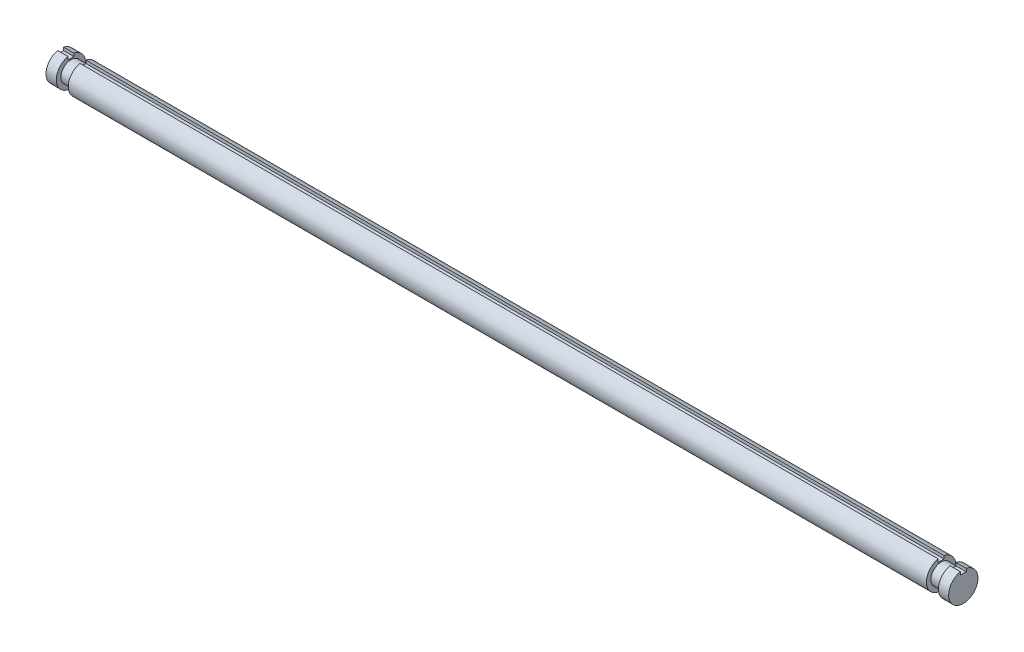
SolidWorks part; units mm, degrees
ref_plane "Front Plane" through (0, 0, 0) normal (1, 0, 0) x (0, 1, 0)
ref_plane "Top Plane" through (0, 0, 0) normal (0, 0, 1) x (0, 1, 0)
ref_plane "Right Plane" through (0, 0, 0) normal (0, 1, 0) x (-1, 0, 0)
sketch "Sketch1" plane through (0, 0, 0) normal (0, 0, 1) x (0, 1, 0)
  line L0 (0, 0) -> (31.7309, 0)
  line L1 (31.7309, 0) -> (31.7309, -22.352)
  line L2 (31.7309, -22.352) -> (22.0218, -22.352)
  line L3 (22.0218, -22.352) -> (22.0218, -48.1584)
  line L4 (22.0218, -48.1584) -> (31.7309, -48.1584)
  line L5 (31.7309, -48.1584) -> (31.7309, -1904.7206)
  line L6 (31.7309, -1904.7206) -> (22.0218, -1904.7206)
  line L7 (22.0218, -1904.7206) -> (22.0218, -1930.527)
  line L8 (22.0218, -1930.527) -> (31.7309, -1930.527)
  line L9 (31.7309, -1930.527) -> (31.7309, -1952.752)
  line L10 (31.7309, -1952.752) -> (0, -1952.752)
  line L11 (0, -1952.752) -> (0, 0)
  line L12 (0, 25.4) -> (0, -1978.152) construction
revolve "Revolve1" add sketch "Sketch1" angle 360 about L12
sketch "Sketch2" plane through (0, 0, 0) normal (1, 0, 0) x (0, 1, 0)
  line L1 (24.6062, -6.35) -> (88.0682, -6.35)
  line L2 (24.6062, -6.35) -> (24.6062, 6.35)
  line L3 (24.6062, 6.35) -> (88.0682, 6.35)
  line L4 (88.0682, -6.35) -> (88.0682, 6.35)
extrude "Cut-Extrude2" cut sketch "Sketch2" along normal blind 1997.456 from offset 22.352 offset against normal yes
